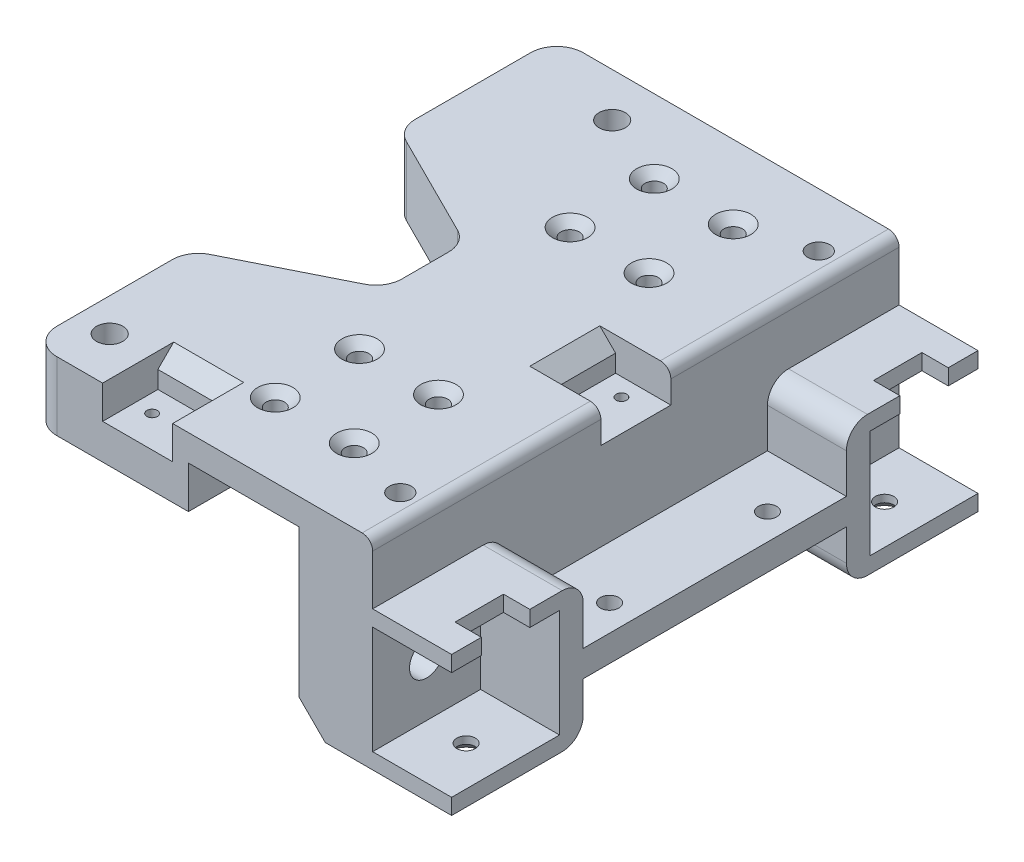
SolidWorks part; units mm, degrees
ref_plane "Front Plane" through (0, 0, 0) normal (0, 0, 1) x (1, 0, 0)
ref_plane "Top Plane" through (0, 0, 0) normal (0, 1, 0) x (1, 0, 0)
ref_plane "Right Plane" through (0, 0, 0) normal (1, 0, 0) x (0, 0, -1)
sketch "Sketch1" plane through (0, 0, 0) normal (0, 1, 0) x (1, 0, 0)
  line L0 (0, 50) -> (0, -50) construction
  line L1 (-10, 50) -> (10, 50)
  line L2 (-10, 50) -> (-10, -50)
  line L3 (-10, -50) -> (10, -50)
  line L4 (10, 50) -> (10, -50) construction
  line L5 (-10, 50) -> (10, -50) construction
  line L6 (-10, -50) -> (10, 50) construction
  line L7 (-7.5, 36) -> (7.5, 36) construction
  line L8 (-7.5, 36) -> (7.5, 20) construction
  line L9 (-10, 0) -> (10, 0) construction
  line L10 (-7.5, -36) -> (7.5, -20) construction
  line L11 (-7.5, -36) -> (7.5, -36) construction
  line L12 (-7.5, 20) -> (7.5, 20) construction
  line L13 (10, 50) -> (11, 50)
  line L14 (11, 50) -> (11, -50)
  line L15 (11, -50) -> (10, -50)
  circle A0 centre (-7.5, 36) radius 1.75
  circle A1 centre (7.5, 36) radius 1.75
  circle A2 centre (-7.5, 20) radius 1.75
  circle A3 centre (7.5, 20) radius 1.75
  circle A4 centre (7.5, -20) radius 1.75
  circle A5 centre (-7.5, -20) radius 1.75
  circle A6 centre (7.5, -36) radius 1.75
  circle A7 centre (-7.5, -36) radius 1.75
  point P0 (0, 0)
  point P16 (0, 36)
  dimension "D2" = 3.5
  dimension "D1" = 20
  dimension "D3" = 15
  dimension "D4" = 16
  dimension "D5" = 100
  dimension "D6" = 20
  dimension "D7" = 1
extrude "Boss-Extrude1" add sketch "Sketch1" along normal blind 5
sketch "Sketch2" plane through (11, 0, 0) normal (1, 0, 0) x (0, 0, -1)
  line L1 (-50, 5) -> (50, 5)
  line L2 (-50, 5) -> (-50, -33)
  line L3 (-50, -33) -> (50, -33)
  line L5 (50, 5) -> (50, -33)
  line L6 (50, 5) -> (50, 0) construction
  line L7 (-50, 5) -> (-50, 0) construction
  line L8 (-50, 5) -> (50, 5) construction
  dimension "D1" = 38
extrude "Boss-Extrude2" add sketch "Sketch2" along normal blind 14
sketch "Sketch3" plane through (25, 0, 0) normal (1, 0, 0) x (0, 0, -1)
  line L0 (0, 5) -> (0, -33) construction
  line L1 (-25, -18) -> (25, -18)
  line L2 (-25, -18) -> (-25, -23)
  line L3 (-25, -23) -> (25, -23)
  line L4 (25, -18) -> (25, -23)
  line L5 (50, 5) -> (-50, 5) construction
  line L6 (-50, -33) -> (50, -33) construction
  point P10 (0, -18)
  dimension "D1" = 5
  dimension "D2" = 50
  dimension "D3" = 10
extrude "Boss-Extrude3" add sketch "Sketch3" along normal blind 15
sketch "Sketch4" plane through (0, -18, 0) normal (0, 1, 0) x (1, 0, 0)
  line L0 (30, 0) -> (40, 0) construction
  line L2 (40, 25) -> (40, -25) construction
  line L3 (35, -15) -> (35, 15) construction
  circle A0 centre (35, 15) radius 1.75
  circle A1 centre (35, -15) radius 1.75
  point P8 (35, 0)
  dimension "D1" = 30
  dimension "D2" = 3.5
  dimension "D3" = 10
extrude "Cut-Extrude1" cut sketch "Sketch4" against normal through all
sketch "Sketch8" plane through (25, 0, 0) normal (1, 0, 0) x (0, 0, -1)
  line L0 (-50, 5) -> (-50, -33) construction
  line L1 (-50, -6.5) -> (-25, -6.5)
  line L2 (-50, -6.5) -> (-50, -9.5)
  line L3 (-50, -33) -> (-25, -33)
  line L4 (-25, -6.5) -> (-25, -33)
  line L5 (-50, -30) -> (-50, -33)
  line L6 (-50, -30) -> (-29.5, -30)
  line L8 (-50, -9.5) -> (-29.5, -9.5)
  line L9 (-29.5, -30) -> (-29.5, -9.5)
  line L10 (0, 20.9) -> (0, -20.9) construction
  line L11 (29.5, -30) -> (29.5, -9.5)
  line L12 (50, -9.5) -> (29.5, -9.5)
  line L13 (50, -30) -> (29.5, -30)
  line L14 (50, -30) -> (50, -33)
  line L15 (25, -6.5) -> (25, -33)
  line L16 (50, -33) -> (25, -33)
  line L17 (50, -6.5) -> (50, -9.5)
  line L18 (50, -6.5) -> (25, -6.5)
  line L19 (-50, -33) -> (50, -33) construction
  line L20 (-25, -18) -> (-25, -23) construction
  dimension "D1" = 3
  dimension "D3" = 3
  dimension "D4" = 20.5
  dimension "D5" = 20.5
extrude "Boss-Extrude6" add sketch "Sketch8" along normal blind 15
sketch "Sketch9" plane through (25, 0, 0) normal (1, 0, 0) x (0, 0, -1)
  line L0 (-50, -9.5) -> (-29.5, -30) construction
  line L1 (50, -9.5) -> (29.5, -30) construction
  circle A0 centre (-39.75, -19.75) radius 3.25
  circle A1 centre (39.75, -19.75) radius 3.25
  dimension "D1" = 6.5
extrude "Cut-Extrude3" cut sketch "Sketch9" against normal through all
sketch "Sketch10" plane through (11, 0, 0) normal (-1, 0, 0) x (0, 0, 1)
  circle A0 centre (-39.75, -19.75) radius 5.25
  circle A1 centre (39.75, -19.75) radius 5.25
  dimension "D1" = 10.5
extrude "Cut-Extrude4" cut sketch "Sketch10" against normal offset from surface (9 mm away) 5 up to face at (25, -19.75, 36.5)
sketch "Sketch11" plane through (0, -6.5, 0) normal (0, 1, 0) x (1, 0, 0)
  line L0 (40, -25) -> (40, -50) construction
  line L1 (40, -35.15) -> (35, -35.15)
  line L2 (40, -35.15) -> (40, -44.35)
  line L3 (40, -44.35) -> (35, -44.35)
  line L4 (35, -35.15) -> (35, -44.35)
  line L5 (35, -39.75) -> (40, -39.75) construction
  line L7 (-10, 0) -> (40, 0) construction
  line L8 (-10, 50) -> (-10, -50) construction
  line L9 (40, 25) -> (40, -25) construction
  line L10 (40, -35.15) -> (35, -35.15)
  line L11 (40, -44.35) -> (35, -44.35)
  line L12 (35, 39.75) -> (40, 39.75) construction
  line L13 (40, 44.35) -> (35, 44.35)
  line L14 (40, 35.15) -> (35, 35.15)
  line L15 (35, 35.15) -> (35, 44.35)
  line L16 (40, 44.35) -> (35, 44.35)
  line L17 (40, 35.15) -> (40, 44.35)
  line L18 (40, 35.15) -> (35, 35.15)
  line L19 (40, -50) -> (40, -29.5) construction
  point P22 (40, -39.75)
  line M7 (40, -50) -> (40, -25)
  dimension "D1" = 9.2
  dimension "D3" = 5
extrude "Cut-Extrude5" cut sketch "Sketch11" against normal up to next contours L1 L4 L3 M7 | L14 L17 L13 L15 region at (37.5, -6.5, 39.75) region at (37.5, -6.5, -39.75)
sketch "Sketch12" plane through (0, -30, 0) normal (0, 1, 0) x (1, 0, 0)
  line L0 (40, -39.75) -> (25, -39.75) construction
  line L1 (40, -29.5) -> (40, -50) construction
  line L2 (25, -25) -> (25, -50) construction
  line L3 (-20.9, 0) -> (20.9, 0) construction
  circle A0 centre (32.5, -39.75) radius 1.75
  circle A2 centre (32.5, 39.75) radius 1.75
  dimension "D1" = 3.5
extrude "Cut-Extrude6" cut sketch "Sketch12" against normal through all
sketch "Sketch13" plane through (-10, 0, 0) normal (-1, 0, 0) x (0, 0, 1)
  line L1 (-50, 5) -> (50, 5)
  line L2 (-50, 5) -> (-50, -8)
  line L3 (-50, -8) -> (50, -8)
  line L4 (50, 5) -> (50, -8)
  dimension "D1" = 13
extrude "Boss-Extrude7" add sketch "Sketch13" along normal blind 30
sketch "Sketch14" plane through (0, 5, 0) normal (0, 1, 0) x (1, 0, 0)
  line L6 (-27.65, 41.65) -> (-27.65, -41.23) construction
  line L12 (-21.15, 35.15) -> (40, 35.15) construction
  line L18 (-33.73, -35.15) -> (40, -35.15) construction
  circle A0 centre (-21.15, 41.65) radius 2.5
  circle A1 centre (-33.73, -41.23) radius 2.5
  circle A2 centre (-33.73, -41.23) radius 6.08 construction
  circle A3 centre (-21.15, 41.65) radius 6.5 construction
  dimension "D1" = 5
  dimension "D2" = 5
  dimension "D4" = 12.16
  dimension "D5" = 13
  dimension "D3" = 21.15
extrude "Cut-Extrude7" cut sketch "Sketch14" against normal through all
sketch "Sketch15" plane through (0, -8, 0) normal (0, -1, 0) x (1, 0, 0)
  line L0 (-40, -50) -> (-40, 50) construction
  line L1 (-29.63, 43.5971) -> (-33.73, 45.9643)
  line L2 (-33.73, 45.9643) -> (-37.83, 43.5971)
  line L3 (-37.83, 43.5971) -> (-37.83, 38.8629)
  line L4 (-37.83, 38.8629) -> (-33.73, 36.4957)
  line L5 (-33.73, 36.4957) -> (-29.63, 38.8629)
  line L6 (-29.63, 38.8629) -> (-29.63, 43.5971)
  line L7 (-17.05, -44.0171) -> (-17.05, -39.2829)
  line L8 (-17.05, -39.2829) -> (-21.15, -36.9157)
  line L9 (-21.15, -36.9157) -> (-25.25, -39.2829)
  line L10 (-25.25, -39.2829) -> (-25.25, -44.0171)
  line L11 (-25.25, -44.0171) -> (-21.15, -46.3843)
  line L12 (-21.15, -46.3843) -> (-17.05, -44.0171)
  circle A0 centre (-33.73, 41.23) radius 4.1 construction
  circle A1 centre (-21.15, -41.65) radius 4.1 construction
  dimension "D1" = 8.2
extrude "Cut-Extrude8" cut sketch "Sketch15" against normal blind 5
sketch "Sketch16" plane through (0, 5, 0) normal (0, 1, 0) x (1, 0, 0)
  line L0 (20, 39.75) -> (40, 39.75) construction
  line L1 (40, 39.75) -> (40, -39.75) construction
  line L2 (40, -39.75) -> (20, -39.75) construction
  line L3 (20, -39.75) -> (20, 39.75) construction
  line L4 (40, 50) -> (40, 29.5) construction
  line L5 (40, -29.5) -> (40, -50) construction
  circle A0 centre (20, 39.75) radius 2.1
  circle A1 centre (20, -39.75) radius 2.1
  dimension "D1" = 4.2
  dimension "D2" = 4.2
  dimension "D3" = 20
extrude "Cut-Extrude9" cut sketch "Sketch16" against normal blind 4
chamfer "Chamfer1" distance 1.6 angle 45 8 edges at (7.5, 5, 34.25) (-7.5, 5, 34.25) (7.5, 5, 18.25) (-7.5, 5, 18.25) (7.5, 5, -18.25) (-7.5, 5, -18.25) (7.5, 5, -34.25) (-7.5, 5, -34.25)
sketch "Sketch17" plane through (0, 5, 0) normal (0, 1, 0) x (1, 0, 0)
  line L0 (-40, 20) -> (-15, 7.5)
  line L1 (-40, -50) -> (-40, 50) construction
  line L2 (-15, 7.5) -> (-15, -7.5)
  line L3 (-15, -7.5) -> (-40, -20)
  line L4 (-40, -20) -> (-40, 20)
  point P5 (-15, 0)
  dimension "D1" = 15
  dimension "D2" = 25
  dimension "D3" = 40
extrude "Cut-Extrude10" cut sketch "Sketch17" against normal through all
chamfer "Chamfer2" distance 1.6 angle 45 2 edges at (32.5, -33, -41.5) (32.5, -33, 41.5)
chamfer "Chamfer3" distance 5 angle 45 1 edges at (11, -33, 0)
sketch "Sketch18" plane through (0, 1, 0) normal (0, 1, 0) x (1, 0, 0)
  circle A0 centre (20, 39.75) radius 1.75
  circle A1 centre (20, -39.75) radius 1.75
  dimension "D1" = 3.5
  dimension "D2" = 3.5
extrude "Cut-Extrude11" cut sketch "Sketch18" against normal blind 4
fillet "Fillet1" radius 5 6 edges at (-40, -1.5, 50) (-40, -1.5, 20) (-15, -1.5, 7.5) (-15, -1.5, -7.5) (-40, -1.5, -20) (-40, -1.5, -50)
fillet "Fillet2" radius 4 4 edges at (32.5, -33, -25) (32.5, -6.5, -25) (32.5, -33, 25) (32.5, -6.5, 25)
sketch "Sketch19" plane through (25, 0, 0) normal (1, 0, 0) x (0, 0, -1)
  line L0 (50, 5) -> (-50, 5) construction
  line L1 (-6.65, 5) -> (6.65, 5)
  line L2 (-6.65, 5) -> (-6.65, -1.3)
  line L3 (-6.65, -1.3) -> (6.65, -1.3)
  line L4 (6.65, 5) -> (6.65, -1.3)
  point P7 (0, 5)
  dimension "D1" = 13.3
  dimension "D2" = 6.3
extrude "Cut-Extrude12" cut sketch "Sketch19" against normal blind 10.5
sketch "Sketch20" plane through (0, -1.3, 0) normal (0, 1, 0) x (1, 0, 0)
  line L0 (19, 3.25) -> (19, -3.25) construction
  line L3 (14.5, 6.65) -> (14.5, -6.65) construction
  line L4 (18, 3.25) -> (18, -3.25) construction
  circle A0 centre (19, 3.25) radius 1
  circle A1 centre (19, -3.25) radius 1
  point P2 (14.5, 0)
  point P3 (19, 0)
  dimension "D1" = 2
  dimension "D2" = 6.5
  dimension "D3" = 3.5
extrude "Cut-Extrude13" cut sketch "Sketch20" against normal blind 3
chamfer "Chamfer4" distance 3 angle 45 1 edges at (14.5, 5, 0)
fillet "Fillet3" radius 2 2 edges at (25, 5, -28.325) (25, 5, 28.325)
sketch "Sketch22" plane through (0, 5, 0) normal (0, 1, 0) x (1, 0, 0)
  line L0 (-35, -50) -> (23, -50) construction
  line L1 (-26.3, -50) -> (-13, -50)
  line L2 (-26.3, -50) -> (-26.3, -39.5)
  line L3 (-26.3, -39.5) -> (-13, -39.5)
  line L4 (-13, -50) -> (-13, -39.5)
  line L5 (-10, 50) -> (-10, -50) construction
  dimension "D1" = 10.5
  dimension "D2" = 13.3
  dimension "D3" = 3
extrude "Cut-Extrude14" cut sketch "Sketch22" against normal blind 6.3
sketch "Sketch23" plane through (0, -1.3, 0) normal (0, 1, 0) x (1, 0, 0)
  line L0 (-22.9, -44) -> (-16.4, -44) construction
  line L2 (-26.3, -50) -> (-13, -50) construction
  line L3 (-22.9, -43) -> (-16.4, -43) construction
  line L4 (-13, -39.5) -> (-26.3, -39.5) construction
  circle A0 centre (-22.9, -44) radius 1
  circle A1 centre (-16.4, -44) radius 1
  point P9 (-19.65, -50)
  point P10 (-19.65, -44)
  dimension "D1" = 2
  dimension "D2" = 2
  dimension "D3" = 6.5
  dimension "D4" = 3.5
extrude "Cut-Extrude15" cut sketch "Sketch23" against normal blind 3
chamfer "Chamfer5" distance 3 angle 45 1 edges at (-19.65, 5, 39.5)
